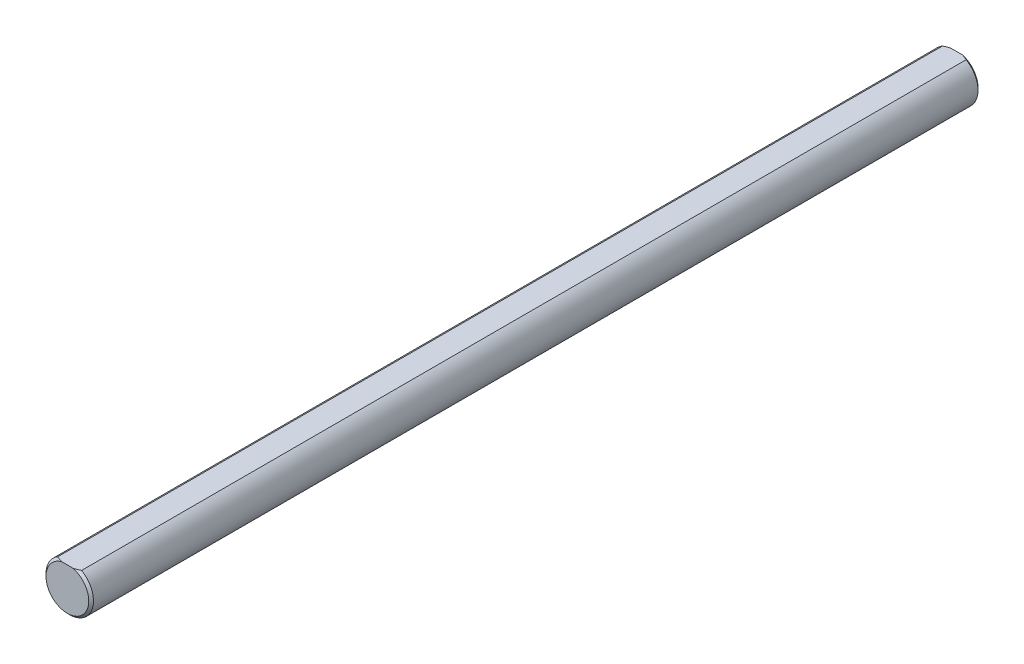
SolidWorks part; units mm, degrees
ref_plane "Front Plane" through (0, 0, 0) normal (0, 0, 1) x (1, 0, 0)
ref_plane "Top Plane" through (0, 0, 0) normal (0, 1, 0) x (1, 0, 0)
ref_plane "Right Plane" through (0, 0, 0) normal (1, 0, 0) x (0, 0, -1)
sketch "Sketch1" plane through (0, 0, 0) normal (0, 0, 1) x (1, 0, 0)
  line L0 (-1.5875, 2.7496) -> (1.5875, 2.7496) construction
  circle A1 centre (0, 0) radius 3.175 construction
  dimension "Diameter" = 6.35
  dimension "Flat Width" = 3.175
sketch "Sketch2" plane through (0, 0, 0) normal (1, 0, 0) x (0, 0, -1)
  line L0 (-59.425, 3.175) -> (59.425, 3.175) construction
  line L1 (0, 3.175) -> (0, -3.175) construction
  line L2 (0, 3.175) -> (0, -3.175) construction
  line L3 (-59.425, 3.175) -> (-59.425, -3.175) construction
  line L4 (-59.425, -3.175) -> (59.425, -3.175) construction
  point P2 (0, 3.175)
  point P3 (46.725, 3.175)
  point P4 (-46.725, 3.175)
  dimension "Length" = 118.85
  dimension "D2" = 12.7
  dimension "D1" = 12.7
  dimension "D-Profile Length" = 118.85
sketch "Sketch3" plane through (0, 0, 0) normal (0, 0, 1) x (1, 0, 0)
  circle A1 centre (0, 0) radius 3.175 construction
  circle A3 centre (0, 0) radius 3.175
extrude "Boss-Extrude2" add sketch "Sketch3" along normal up to vertex (59.425 mm away) and the other way up to vertex (59.425 mm away) up to point (0, 3.175, 59.425) other way up to point (0, 3.175, -59.425)
sketch "Sketch10" plane through (0, 0, 0) normal (0, 0, 1) x (1, 0, 0)
  line L0 (-1.5875, 2.7496) -> (1.5875, 2.7496)
  line L1 (0, 0) -> (0, 3.175) construction
  circle A0 centre (0, 0) radius 3.175 construction
  circle A1 centre (0, 0) radius 3.175 construction
  arc A2 (-1.5875, 2.7496) -> (1.5875, 2.7496) centre (0, 0) cw
extrude "Cut-Extrude5" cut sketch "Sketch10" against normal through all both and the other way through all
chamfer "Chamfer1" distance 0.3175 angle 45 2 edges at (0, -3.175, 59.425) (0, -3.175, -59.425)
equation "\"D1@Chamfer1\"= \"Diameter@Sketch1\" / 20"
equation "\"D1@Sketch2\"=\"Diameter@Sketch1\"*2"
equation "\"D2@Sketch2\"=\"D1@Sketch2\""
